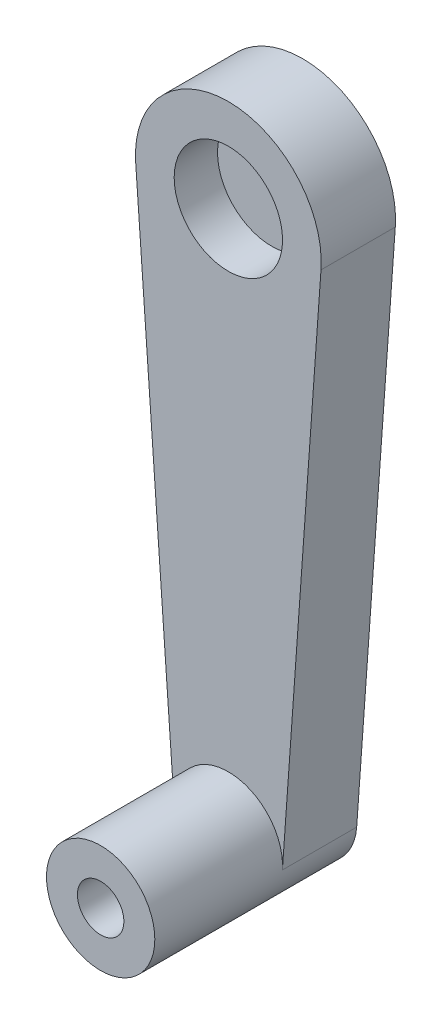
SolidWorks part; units mm, degrees
ref_plane "Front Plane" through (0, 0, 0) normal (0, 0, 1) x (1, 0, 0)
ref_plane "Top Plane" through (0, 0, 0) normal (0, 1, 0) x (1, 0, 0)
ref_plane "Right Plane" through (0, 0, 0) normal (1, 0, 0) x (0, 0, -1)
sketch "Sketch1" plane through (0, 0, 0) normal (0, 0, 1) x (1, 0, 0)
  circle A0 centre (0, 0) radius 1.5
  circle A1 centre (0, 0) radius 3.5
  dimension "D1" = 3
  dimension "D2" = 7
extrude "Boss-Extrude1" add sketch "Sketch1" along normal blind 8.25
sketch "Sketch2" plane through (0, 0, 0) normal (0, 0, -1) x (-1, 0, 0)
  line L0 (-5.9847, 34.5714) -> (-3.4911, -0.25)
  line L1 (5.9847, 34.5714) -> (3.4911, -0.25)
  circle A0 centre (0, 35) radius 3.5
  circle A1 centre (0, 35) radius 6
  circle A2 centre (0, 0) radius 3.5 construction
  arc A3 (-3.4911, -0.25) -> (3.4911, -0.25) centre (0, 0) ccw
  circle M4 centre (0, 0) radius 3.5
  circle M5 centre (0, 0) radius 1.5
  dimension "D1" = 7
  dimension "D2" = 12
  dimension "D3" = 35
extrude "Boss-Extrude2" add sketch "Sketch2" along normal blind 2.8 contours A1 L0 L1 M4 | A1 A0 | M4 M5 | M5 region at (0, 17.3997, 0) region at (0.2084, 40.8266, 0) region at (0.1215, 3.3988, 0) region at (0, 0, 0)
extrude "Boss-Extrude3" add sketch "Sketch2<3>" along normal blind 2 from surface contours A1 A0 | A1 L0 L1 M4 | M4 M5 | A0 | M5 region at (0, 17.3997, 0) region at (0.2084, 40.8266, 0) region at (0.1215, 3.3988, 0) region at (0, 35, 0) region at (0, 0, 0) starting at face at (0, 17.9554, -2.8)
sketch "Sketch2<3>" plane through (0, 0, 0) normal (0, 0, -1) x (-1, 0, 0) same geometry as "Sketch2"
